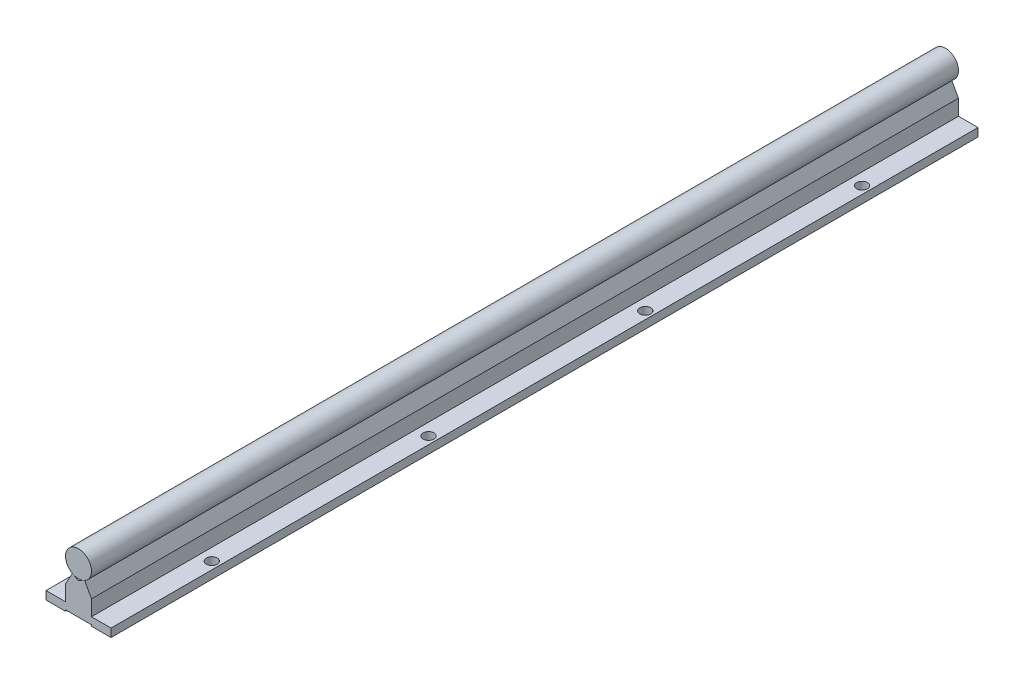
SolidWorks part; units mm, degrees
ref_plane "Alzado" through (0, 0, 0) normal (0, 0, 1) x (1, 0, 0)
ref_plane "Planta" through (0, 0, 0) normal (0, 1, 0) x (1, 0, 0)
ref_plane "Vista lateral" through (0, 0, 0) normal (1, 0, 0) x (0, 0, -1)
sketch "Croquis1" plane through (0, 0, 0) normal (0, 0, 1) x (1, 0, 0)
  line L0 (0, 0) -> (0, -22) construction
  line L1 (0, -22) -> (15, -22) construction
  line L2 (3.5, 0) -> (3.5, -22) construction
  line L3 (6, -22) -> (6, 5.4102) construction
  line L4 (-13.9204, -11) -> (10.0172, -11) construction
  line L5 (0, -6.8) -> (2.8235, -5.2941)
  line L6 (2.8235, -5.2941) -> (6, -11)
  line L7 (6, -11) -> (6, -18.2)
  line L8 (6, -18.2) -> (15, -18.2)
  line L9 (15, -18.2) -> (15, -22)
  line L10 (-6, -21.4) -> (6, -21.4)
  line L11 (6, -21.4) -> (6, -22)
  line L12 (6, -22) -> (15, -22)
  line L13 (-6, -21.4) -> (-6, -22)
  line L14 (-6, -22) -> (-15, -22)
  line L15 (-15, -18.2) -> (-15, -22)
  line L16 (-6, -18.2) -> (-15, -18.2)
  line L17 (-6, -11) -> (-6, -18.2)
  line L18 (-2.8235, -5.2941) -> (-6, -11)
  line L19 (0, -6.8) -> (-2.8235, -5.2941)
  circle A0 centre (0, 0) radius 6
  point P17 (0, -6)
  point P21 (0, -21.4)
  dimension "D1" = 12
  dimension "D2" = 22
  dimension "D3" = 15
  dimension "D4" = 3.5
  dimension "D5" = 6
  dimension "D6" = 11
  dimension "D7" = 0.8
  dimension "D8" = 3.8
  dimension "D9" = 0.6
extrude "Saliente-Extruir1" add sketch "Croquis1" along normal blind 400 contours L5 L19 L18 L17 L16 L15 L14 L13 L10 L11 L12 L9 L8 L7 L6 | A0 region at (0, -15.8774, 0) region at (0, 0, 0)
sketch "Croquis2" plane through (0, -18.2, 0) normal (0, 1, 0) x (1, 0, 0)
  line L0 (-11.5, 0) -> (-11.5, -400) construction
  line L1 (-6, 0) -> (-15, 0) construction
  line L2 (-6, -400) -> (-15, -400) construction
  line L3 (-15, -400) -> (-15, 0) construction
  circle A0 centre (-11.5, -50) radius 2.5
  circle A1 centre (-11.5, -150) radius 2.5
  circle A2 centre (-11.5, -250) radius 2.5
  circle A3 centre (-11.5, -350) radius 2.5
  circle A4 centre (-11.5, -450) radius 2.5
  dimension "D2" = 5
  dimension "D1" = 3.5
  dimension "D3" = 50
  dimension "D4" = 5
extrude "Cortar-Extruir1" cut sketch "Croquis2" against normal up to surface (3.8 mm away) up to face at (-10.5, -22, 200)
mirror "Simetría1" about plane through (0, 0, 0) normal (1, 0, 0) of "Cortar-Extruir1"
equation "\"D4@Croquis1\"=7/2"
